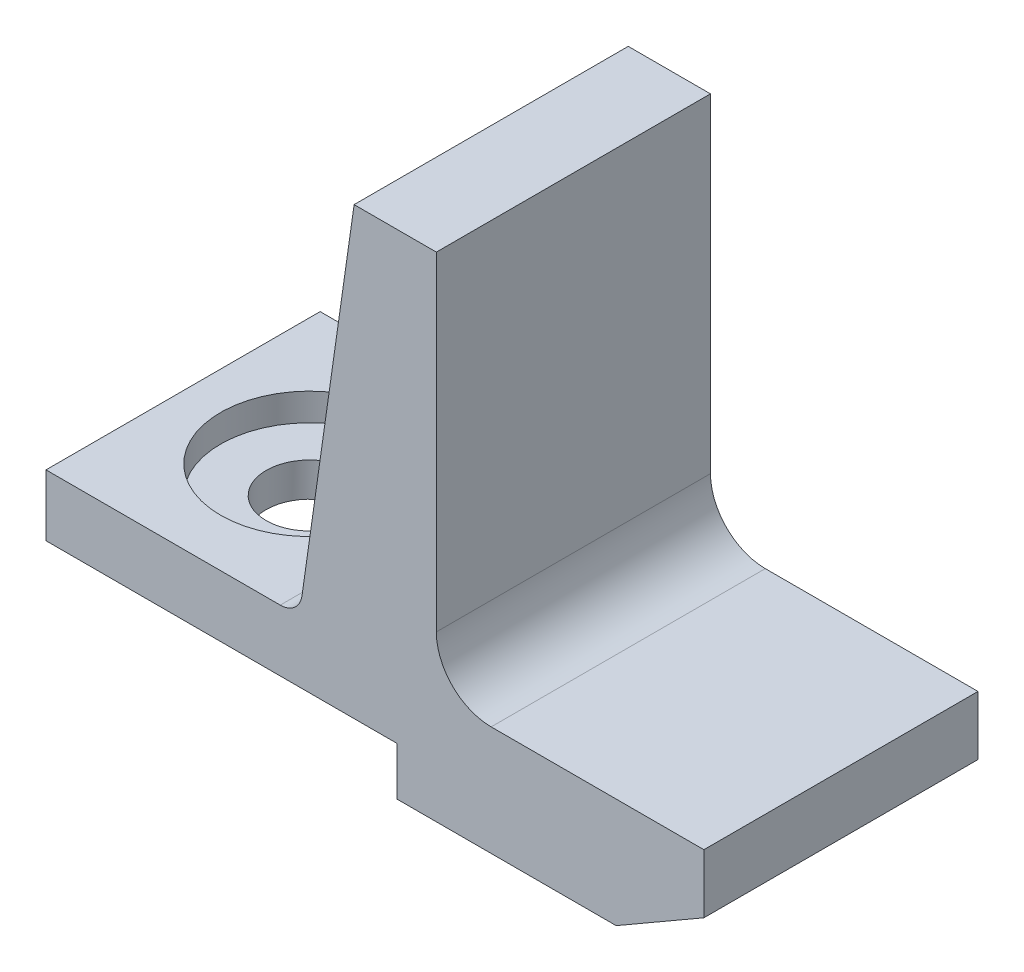
SolidWorks part; units mm, degrees
ref_plane "Front Plane" through (0, 0, 0) normal (0, 0, 1) x (1, 0, 0)
ref_plane "Top Plane" through (0, 0, 0) normal (0, 1, 0) x (1, 0, 0)
ref_plane "Right Plane" through (0, 0, 0) normal (1, 0, 0) x (0, 0, -1)
sketch "Sketch1" plane through (0, 0, 0) normal (0, 0, 1) x (1, 0, 0)
  line L0 (0, 0) -> (30.988, 0)
  line L1 (30.988, 0) -> (30.988, -12.7)
  line L2 (30.988, -12.7) -> (-4.572, -12.7)
  line L3 (-45.212, -7.112) -> (-45.212, 0)
  line L4 (-45.212, 0) -> (-15.875, 0)
  line L5 (-15.875, 0) -> (-9.525, 44.45)
  line L6 (-9.525, 44.45) -> (0, 44.45)
  line L7 (0, 44.45) -> (0, 0)
  line L8 (-4.572, -12.7) -> (-4.572, -7.112)
  line L9 (-4.572, -7.112) -> (-45.212, -7.112)
  dimension "D1" = 30.988
  dimension "D2" = 44.45
  dimension "D3" = 12.7
  dimension "D4" = 76.2
  dimension "D5" = 9.525
  dimension "D6" = 5.588
  dimension "D7" = 40.64
  dimension "D8" = 15.875
extrude "Boss-Extrude1" add sketch "Sketch1" along normal blind 31.75
hole_wizard "CBORE for 3/8 Binding Head Machine Screw1" positions "Sketch6" profile "Sketch3" counterbore size "3/8" standard "ANSI Inch" end condition through all
sketch "Sketch6" plane through (0, 0, 0) normal (0, 1, 0) x (1, 0, 0)
  line L0 (-15.875, 0) -> (-45.212, 0) construction
  line L1 (-45.212, -31.75) -> (-45.212, 0) construction
  point P0 (-30.5435, -15.875)
  point P5 (-30.5435, 0)
  point P8 (-45.212, -15.875)
sketch "Sketch3" plane through (-30.5435, 0, 15.875) normal (1, 0, 0) x (0, 0, 1)
  line L0 (0, 0) -> (0, 12.7)
  line L1 (0, 12.7) -> (5.0419, 12.7)
  line L3 (5.0419, 12.7) -> (5.0419, 3.175)
  line L4 (10.3187, 3.175) -> (5.0419, 3.175)
  line L5 (10.3187, 3.175) -> (10.3187, 0)
  line L7 (10.3187, 0) -> (0, 0)
  line L11 (0, 0) -> (0, 107.95) construction
  dimension "Thru Hole Dia." = 10.0838
  dimension "Thru Hole Depth" = 12.7
  dimension "C'Bore Depth" = 3.175
chamfer "Chamfer1" distance 10.16 angle 30 1 edges at (30.988, -12.7, 15.875) first distance on face at (13.208, -12.7, 15.875)
fillet "Fillet1" radius 2.54 1 edges at (-15.875, 0, 15.875)
fillet "Fillet2" radius 6.35 1 edges at (0, 0, 15.875)
